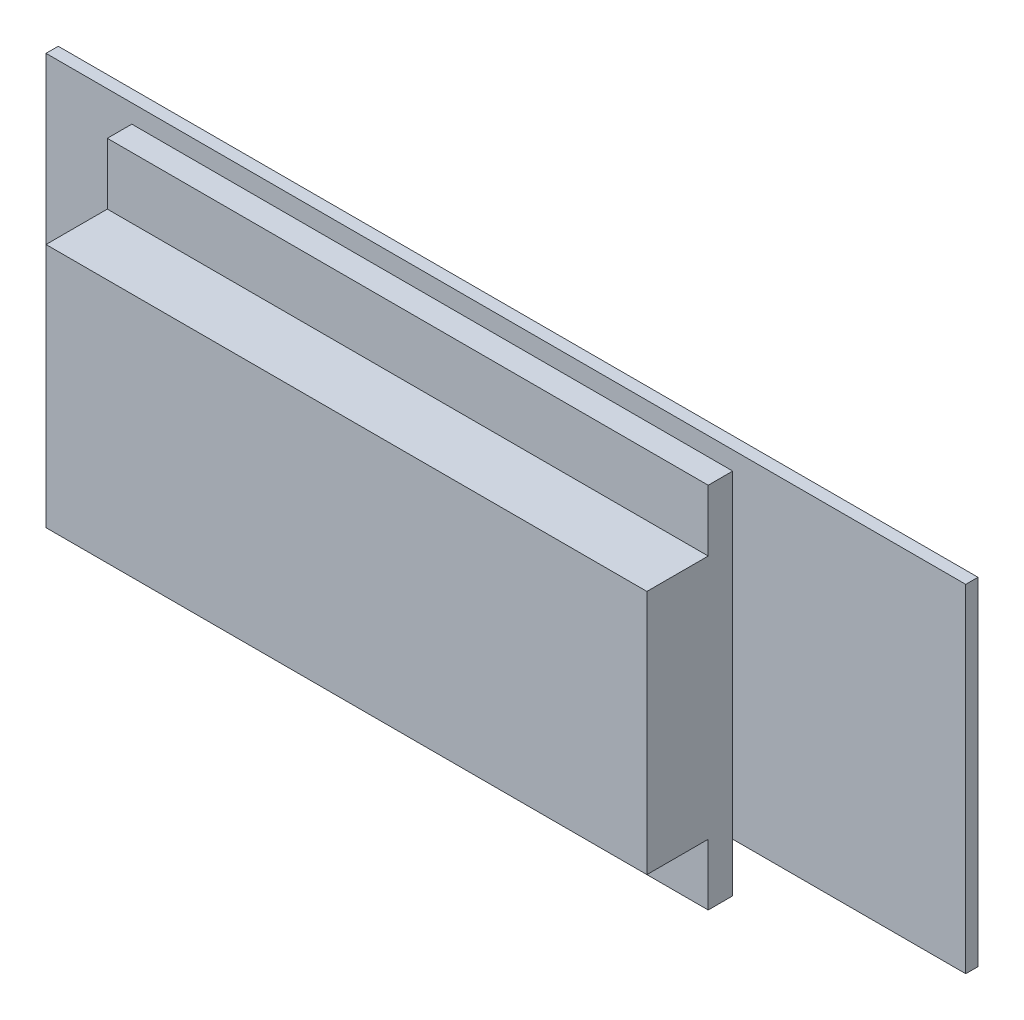
SolidWorks part; units mm, degrees
ref_plane "Piano frontale" through (0, 0, 0) normal (0, 0, 1) x (1, 0, 0)
ref_plane "Piano superiore" through (0, 0, 0) normal (0, 1, 0) x (1, 0, 0)
ref_plane "Piano destro" through (0, 0, 0) normal (1, 0, 0) x (0, 0, -1)
sketch "Schizzo1" plane through (0, 0, 0) normal (0, 0, 1) x (1, 0, 0)
  line L0 (-75, 57.9268) -> (-75, -67.107) construction
  line L1 (75, -27.5) -> (-75, -27.5)
  line L2 (75, -27.5) -> (75, 27.5)
  line L3 (75, 27.5) -> (-75, 27.5)
  line L4 (-75, -27.5) -> (-75, 27.5)
  line L5 (75, -27.5) -> (-75, 27.5) construction
  line L6 (75, 27.5) -> (-75, -27.5) construction
  line L7 (-61, 24.5) -> (-61, -35.5) construction
  line L8 (37, 24.5) -> (37, -35.5) construction
  line L9 (-110.8967, 27.5) -> (115.6497, 27.5) construction
  line L10 (-61, 24.5) -> (37, 24.5) construction
  line L12 (-61, -35.5) -> (37, -35.5) construction
  line L13 (-61, 57.9268) -> (-61, -67.107) construction
  line L14 (-110.8967, 24.5) -> (115.6497, 24.5) construction
  line L15 (37, 57.9268) -> (37, -67.107) construction
  point P0 (0, 0)
  point P16 (-111.3967, -34.5)
  point P17 (115.1497, -34.5)
  dimension "D1" = 150
  dimension "D2" = 55
  dimension "D3" = 14
  dimension "D4" = 98
  dimension "D5" = 3
extrude "Estrusione-Estrusione1" add sketch "Schizzo1" along normal blind 2
sketch "Schizzo2" plane through (0, 0, 2) normal (0, 0, 1) x (1, 0, 0)
  line L0 (-61, 24.5) -> (-61, -35.5) construction
  line L1 (-61, 24.5) -> (37, 24.5) construction
  line L2 (37, 24.5) -> (37, -35.5) construction
  line L3 (-61, -35.5) -> (37, -35.5) construction
  line L12 (-61, 24.5) -> (-61, -35.5)
  line L13 (-61, 24.5) -> (37, 24.5)
  line L14 (37, 24.5) -> (37, -35.5)
  line L15 (-61, -35.5) -> (37, -35.5)
extrude "Estrusione-Estrusione2" add sketch "Schizzo2" along normal blind 4
sketch "Schizzo3" plane through (0, 0, 6) normal (0, 0, 1) x (1, 0, 0)
  line L0 (-61, 24.5) -> (37, 24.5) construction
  line L1 (-61, -35.5) -> (37, -35.5) construction
  line L2 (-61, 14.5) -> (37, 14.5)
  line L3 (-61, -25.5) -> (37, -25.5)
  line L4 (-61, 14.5) -> (-61, -25.5)
  line L5 (37, 14.5) -> (37, -25.5)
  dimension "D1" = 10
  dimension "D2" = 10
extrude "Estrusione-Estrusione3" add sketch "Schizzo3" along normal blind 10
sketch "Schizzo4" plane through (0, 0, 2) normal (0, 0, 1) x (1, 0, 0)
  line L0 (19.3715, 27.5) -> (126.3979, 27.5) construction
  line L1 (75, 27.5) -> (-75, 27.5) construction
  line L2 (19.3715, -2.5) -> (126.3979, -2.5) construction
  line L3 (75, 27.5) -> (75, -66.319) construction
  line L4 (62, 27.5) -> (62, -66.319) construction
  line L6 (37, 23.4564) -> (37, 61.9788) construction
  line L7 (37, 24.5) -> (37, -35.5) construction
  line L8 (75, 23.4564) -> (75, 61.9788)
  circle A0 centre (62, -2.5) radius 4
  dimension "D4" = 8
  dimension "D3" = 38
  dimension "D1" = 30
  dimension "D2" = 13
sketch "Schizzo5" plane through (0, 0, 2) normal (0, 0, 1) x (1, 0, 0)
  line L0 (62, -2.5) -> (93.3196, -2.5) construction
  line L1 (62, -19.5) -> (93.3196, -19.5) construction
  line L2 (62, -2.5) -> (62, -19.5) construction
  dimension "D1" = 17
